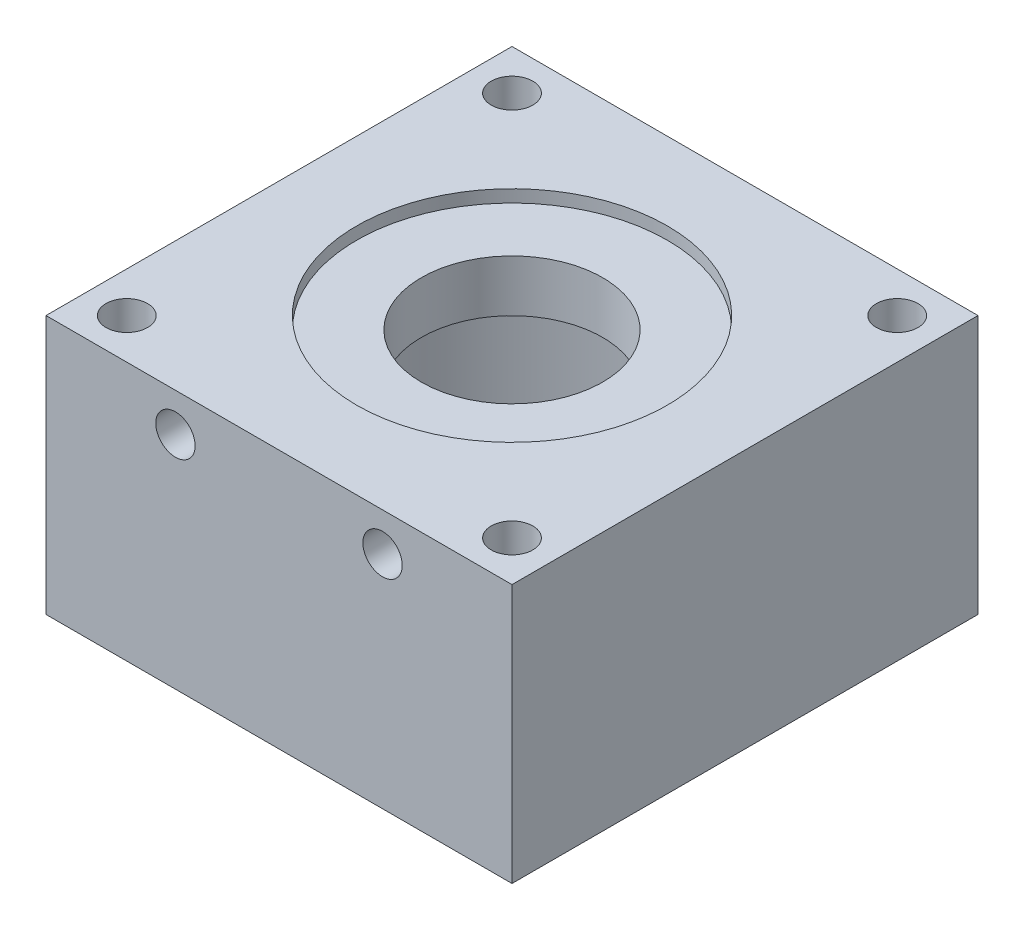
SolidWorks part; units mm, degrees
material "6061 Alloy"
ref_plane "Front" through (0, 0, 0) normal (0, 0, 1) x (1, 0, 0)
ref_plane "Top" through (0, 0, 0) normal (0, 1, 0) x (1, 0, 0)
ref_plane "Right" through (0, 0, 0) normal (1, 0, 0) x (0, 0, -1)
sketch "Sketch1" plane through (0, 0, 0) normal (0, 1, 0) x (1, 0, 0)
  line L1 (-28.575, 28.575) -> (28.575, 28.575)
  line L2 (-28.575, 28.575) -> (-28.575, -28.575)
  line L3 (-28.575, -28.575) -> (28.575, -28.575)
  line L4 (28.575, 28.575) -> (28.575, -28.575)
  line L5 (-28.575, 28.575) -> (28.575, -28.575) construction
  line L6 (-28.575, -28.575) -> (28.575, 28.575) construction
  line L7 (-23.622, 23.622) -> (23.622, 23.622) construction
  line L8 (-23.622, 23.622) -> (-23.622, -23.622) construction
  line L9 (-23.622, -23.622) -> (23.622, -23.622) construction
  line L10 (23.622, 23.622) -> (23.622, -23.622) construction
  line L11 (-23.622, 23.622) -> (23.622, -23.622) construction
  line L12 (-23.622, -23.622) -> (23.622, 23.622) construction
  circle A0 centre (23.622, -23.622) radius 2.5527
  circle A1 centre (23.622, 23.622) radius 2.5527
  circle A2 centre (-23.622, 23.622) radius 2.5527
  circle A3 centre (-23.622, -23.622) radius 2.5527
  point P0 (0, 0)
  point P6 (0, 0)
  dimension "D3" = 5.1054
  dimension "D1" = 57.15
  dimension "D2" = 47.244
extrude "Boss-Extrude1" add sketch "Sketch1" along normal blind 31.75
sketch "Sketch2" plane through (0, 31.75, 0) normal (0, 1, 0) x (1, 0, 0)
  circle A0 centre (0, 0) radius 19.05
  dimension "D1" = 38.1
extrude "Cut-Extrude1" cut sketch "Sketch2" against normal blind 1.524
sketch "Sketch3" plane through (0, 30.226, 0) normal (0, 1, 0) x (1, 0, 0)
  circle A0 centre (0, 0) radius 11.1125
  dimension "D1" = 22.225
extrude "Cut-Extrude2" cut sketch "Sketch3" against normal through all
sketch "Sketch4" plane through (0, 0, 0) normal (0, -1, 0) x (1, 0, 0)
  line L0 (0, 0) -> (0, 28.575) construction
  line L1 (-28.575, 28.575) -> (28.575, 28.575) construction
  line L2 (0, 0) -> (13.0457, 20.2994) construction
  circle A0 centre (0, 0) radius 21.844 construction
  circle A1 centre (0, 0) radius 24.13 construction
  arc A2 (0, 20.955) -> (2.8224, 22.6758) centre (0, 24.13) ccw
  arc A3 (11.3291, 17.6285) -> (9.8851, 20.602) centre (13.0457, 20.2994) cw
  arc A4 (2.8224, 22.6758) -> (9.8851, 20.602) centre (6.1542, 20.9592) cw
  arc A5 (11.3291, 17.6285) -> (14.6338, 17.5502) centre (13.0457, 20.2994) ccw
  arc A6 (14.6338, 17.5502) -> (19.4542, 11.9872) centre (16.5086, 14.3048) cw
  arc A7 (19.0613, 8.705) -> (19.4542, 11.9872) centre (21.9494, 10.024) cw
  arc A8 (19.0613, 8.705) -> (21.7991, 6.8525) centre (21.9494, 10.024) ccw
  arc A9 (21.7991, 6.8525) -> (22.8467, -0.4334) centre (21.6217, 3.1087) cw
  arc A10 (20.7417, -2.9822) -> (22.8467, -0.4334) centre (23.8844, -3.4341) cw
  arc A11 (20.7417, -2.9822) -> (22.0433, -6.0208) centre (23.8844, -3.4341) ccw
  arc A12 (22.0433, -6.0208) -> (18.9855, -12.7165) centre (19.87, -9.0743) cw
  arc A13 (15.8367, -13.7226) -> (18.9855, -12.7165) centre (18.2362, -15.8018) cw
  arc A14 (15.8367, -13.7226) -> (15.289, -16.9825) centre (18.2362, -15.8018) ccw
  arc A15 (15.289, -16.9825) -> (9.0966, -20.9621) centre (11.8098, -18.3763) cw
  arc A16 (5.9037, -20.1062) -> (9.0966, -20.9621) centre (6.7982, -23.1526) cw
  arc A17 (5.9037, -20.1062) -> (3.6804, -22.5524) centre (6.7982, -23.1526) ccw
  arc A18 (3.6804, -22.5524) -> (-3.6804, -22.5524) centre (0, -21.844) cw
  arc A19 (-5.9037, -20.1062) -> (-3.6804, -22.5524) centre (-6.7982, -23.1526) cw
  arc A20 (-5.9037, -20.1062) -> (-9.0966, -20.9621) centre (-6.7982, -23.1526) ccw
  arc A21 (-9.0966, -20.9621) -> (-15.289, -16.9825) centre (-11.8098, -18.3763) cw
  arc A22 (-15.8367, -13.7226) -> (-15.289, -16.9825) centre (-18.2362, -15.8018) cw
  arc A23 (-15.8367, -13.7226) -> (-18.9855, -12.7165) centre (-18.2362, -15.8018) ccw
  arc A24 (-18.9855, -12.7165) -> (-22.0433, -6.0208) centre (-19.87, -9.0743) cw
  arc A25 (-20.7417, -2.9822) -> (-22.0433, -6.0208) centre (-23.8844, -3.4341) cw
  arc A26 (-20.7417, -2.9822) -> (-22.8467, -0.4334) centre (-23.8844, -3.4341) ccw
  arc A27 (-22.8467, -0.4334) -> (-21.7991, 6.8525) centre (-21.6217, 3.1087) cw
  arc A28 (-19.0613, 8.705) -> (-21.7991, 6.8525) centre (-21.9494, 10.024) cw
  arc A29 (-19.0613, 8.705) -> (-19.4542, 11.9872) centre (-21.9494, 10.024) ccw
  arc A30 (-19.4542, 11.9872) -> (-14.6338, 17.5502) centre (-16.5086, 14.3048) cw
  arc A31 (-11.3291, 17.6285) -> (-14.6338, 17.5502) centre (-13.0457, 20.2994) cw
  arc A32 (-11.3291, 17.6285) -> (-9.8851, 20.602) centre (-13.0457, 20.2994) ccw
  arc A33 (-9.8851, 20.602) -> (-2.8224, 22.6758) centre (-6.1542, 20.9592) cw
  arc A34 (0, 20.955) -> (-2.8224, 22.6758) centre (0, 24.13) cw
  point P87 (0, 0)
  dimension "D1" = 48.26
  dimension "D2" = 43.688
  dimension "D4" = 3.175
  dimension "D5" = 3.175
  dimension "D3" = 32.727
  dimension "D6" = 11
extrude "Cut-Extrude3" cut sketch "Sketch4" against normal blind 23.876
sketch "Sketch5" plane through (0, 0, 0) normal (0, -1, 0) x (1, 0, 0)
  circle A0 centre (0, 0) radius 26.1937
  dimension "D1" = 52.3875
extrude "Cut-Extrude4" cut sketch "Sketch5" against normal blind 17.526
sketch "Sketch7" plane through (0, 0, 0) normal (0, -1, 0) x (1, 0, 0)
  line L4 (-28.575, -28.575) -> (-28.575, 28.575) construction
  line L5 (-23.8125, 26.9875) -> (23.8125, 26.9875)
  line L6 (-26.9875, 23.8125) -> (-26.9875, -23.8125)
  line L7 (-23.8125, -26.9875) -> (23.8125, -26.9875)
  line L8 (26.9875, 23.8125) -> (26.9875, -23.8125)
  line L9 (-26.9875, 26.9875) -> (26.9875, -26.9875) construction
  line L10 (-26.9875, -26.9875) -> (26.9875, 26.9875) construction
  line L11 (28.575, -28.575) -> (-28.575, -28.575) construction
  arc A0 (-26.9875, -23.8125) -> (-23.8125, -26.9875) centre (-23.8125, -23.8125) ccw
  arc A2 (23.8125, -26.9875) -> (26.9875, -23.8125) centre (23.8125, -23.8125) ccw
  arc A3 (23.8125, 26.9875) -> (26.9875, 23.8125) centre (23.8125, 23.8125) cw
  arc A4 (-23.8125, 26.9875) -> (-26.9875, 23.8125) centre (-23.8125, 23.8125) ccw
  point P0 (0, 0)
  dimension "D1" = 1.5875
  dimension "D3" = 3.175
  dimension "D2" = 1.5875
extrude "Cut-Extrude5" cut sketch "Sketch7" against normal blind 3.175
hole_wizard "#10-32 Tapped Hole1" positions "Sketch9" profile "Sketch8" tap size "#10-32" standard "ANSI Inch"
sketch "Sketch9" plane through (0, 0, 28.575) normal (0, 0, 1) x (1, 0, 0)
  line L0 (12.7, 27.051) -> (-12.7, 27.051) construction
  line L2 (0, 27.051) -> (0, 31.75) construction
  line L3 (-28.575, 31.75) -> (28.575, 31.75) construction
  line L5 (-11.1125, 23.876) -> (11.1125, 23.876) construction
  point P0 (12.7, 27.051)
  point P2 (-12.7, 27.051)
  dimension "D1" = 3.175
  dimension "D2" = 25.4
sketch "Sketch8" plane through (12.7, 27.051, 28.575) normal (1, 0, 0) x (0, -1, 0)
  line L0 (0, 0) -> (0, 13.9133)
  line L1 (0, 13.9133) -> (2.0193, 12.7)
  line L2 (2.0193, 12.7) -> (2.0193, 9.652)
  line L3 (2.0193, 9.652) -> (2.413, 9.652)
  line L4 (2.413, 9.652) -> (2.413, 0)
  line L5 (2.413, 0) -> (0, 0)
  line L10 (0, 13.9133) -> (-2.0193, 12.7) construction
  line L11 (0, -6.35) -> (0, 107.95) construction
  dimension "Tap Drill Dia." = 4.0386
  dimension "Tap Drill Depth" = 12.7
  dimension "Thread Major Dia." = 4.826
  dimension "Thread Depth" = 9.652
  dimension "Drill Angle" = 118
